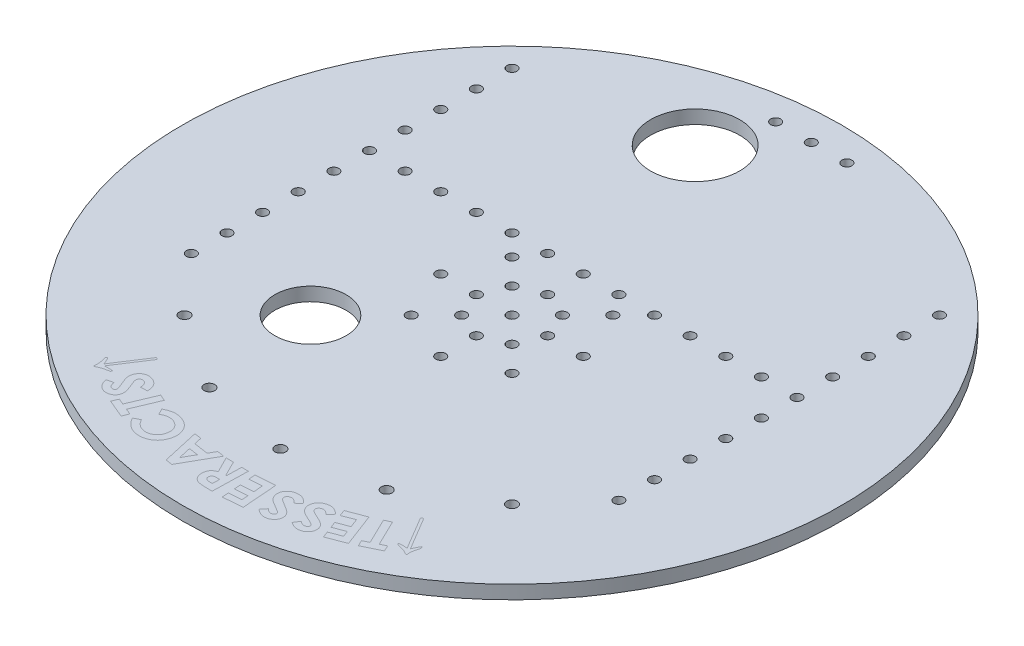
SolidWorks part; units mm, degrees
material "Balsa"
ref_plane "Front Plane" through (0, 0, 0) normal (0, 0, 1) x (1, 0, 0)
ref_plane "Top Plane" through (0, 0, 0) normal (0, 1, 0) x (1, 0, 0)
ref_plane "Right Plane" through (0, 0, 0) normal (1, 0, 0) x (0, 0, -1)
sketch "Sketch1" plane through (0, 0, 0) normal (0, 1, 0) x (1, 0, 0)
  circle A0 centre (0, 0) radius 117.475
  dimension "D1" = 234.95
extrude "Boss-Extrude1" add sketch "Sketch1" against normal blind 4.826
sketch "Sketch3" plane through (0, 0, 0) normal (0, 1, 0) x (1, 0, 0)
  line L1 (-114.4075, 26.67) -> (-88.9, 26.67)
  line L2 (0, -92.075) -> (0, -117.475)
  line L3 (-88.9, -26.67) -> (-88.9, 26.67)
  line L4 (0, 0) -> (-88.9, 0) construction
  line L5 (0, 0) -> (0, -117.475) construction
  line L6 (0, 0) -> (0, 117.475) construction
  line L8 (-88.9, -26.67) -> (-114.4075, -26.67)
  line L10 (-84.6624, -36.195) -> (-111.76, -36.195)
  arc A0 (-114.4075, 26.67) -> (-114.4075, -26.67) centre (0, 0) ccw
  circle A1 centre (0, 0) radius 117.475 construction
  arc A3 (-84.6624, -36.195) -> (0, -92.075) centre (0, 0) ccw
  arc A4 (-111.76, -36.195) -> (0, -117.475) centre (0, 0) ccw
  dimension "D1" = 88.9
  dimension "D2" = 53.34
  dimension "D4" = 9.525
  dimension "D5" = 25.4
extrude "Cut-Extrude4" [suppressed] cut sketch "Sketch3" against normal through all
fillet "Fillet1" [suppressed] radius 2.54
mirror "Mirror1" [suppressed] about plane through (0, 0, 0) normal (1, 0, 0)
sketch "Sketch4" plane through (0, 0, 0) normal (0, 1, 0) x (1, 0, 0)
  line L0 (-76.2, 38.1) -> (-76.2, 25.4) construction
  line L1 (-76.2, 25.4) -> (-76.2, 12.7) construction
  line L2 (-76.2, 12.7) -> (-76.2, 0) construction
  line L3 (-76.2, 0) -> (-76.2, -12.7) construction
  line L4 (-76.2, -12.7) -> (-76.2, -25.4) construction
  line L5 (-76.2, -25.4) -> (-76.2, -38.1) construction
  line L6 (0, 0) -> (-76.2, 0) construction
  line L12 (-76.2, 76.2) -> (-76.2, 63.5) construction
  line L13 (-76.2, 63.5) -> (-76.2, 50.8) construction
  line L14 (-76.2, 50.8) -> (-76.2, 38.1) construction
  circle A0 centre (-76.2, 0) radius 1.778
  circle A1 centre (-76.2, 12.7) radius 1.778
  circle A2 centre (-76.2, 25.4) radius 1.778
  circle A3 centre (-76.2, 38.1) radius 1.778
  circle A4 centre (-76.2, -12.7) radius 1.778
  circle A5 centre (-76.2, -25.4) radius 1.778
  circle A6 centre (-76.2, -38.1) radius 1.778
  circle A7 centre (-76.2, 50.8) radius 1.778
  circle A8 centre (-76.2, 63.5) radius 1.778
  circle A9 centre (-76.2, 76.2) radius 1.778
  dimension "D2" = 3.556
  dimension "D1" = 12.7
  dimension "D3" = 76.2
extrude "Cut-Extrude5" cut sketch "Sketch4" against normal through all
mirror "Mirror3" about plane through (0, 0, 0) normal (1, 0, 0) of "Cut-Extrude5"
sketch "Sketch5" plane through (0, 0, 0) normal (0, 1, 0) x (1, 0, 0)
  circle A0 centre (0, 0) radius 1.778
  dimension "D1" = 3.556
extrude "Cut-Extrude6" cut sketch "Sketch5" against normal through all
sketch "Sketch6" plane through (0, 0, 0) normal (0, 1, 0) x (1, 0, 0)
  line L0 (0, 0) -> (0, 25.4) construction
  line L1 (0, 25.4) -> (12.7, 25.4) construction
  line L2 (12.7, 25.4) -> (25.4, 25.4) construction
  line L3 (25.4, 25.4) -> (38.1, 25.4) construction
  line L4 (-38.1, 25.4) -> (-50.8, 25.4) construction
  line L5 (38.1, 25.4) -> (50.8, 25.4) construction
  line L6 (0, 25.4) -> (-12.7, 25.4) construction
  line L7 (-12.7, 25.4) -> (-25.4, 25.4) construction
  line L8 (-25.4, 25.4) -> (-38.1, 25.4) construction
  line L9 (-50.8, 25.4) -> (-63.5, 25.4) construction
  line L10 (50.8, 25.4) -> (63.5, 25.4) construction
  line L11 (0, 106.68) -> (12.7, 106.68) construction
  line L12 (12.7, 106.68) -> (25.4, 106.68) construction
  line L13 (25.4, 106.68) -> (38.1, 106.68) construction
  line L14 (-38.1, 106.68) -> (-50.8, 106.68) construction
  line L15 (38.1, 106.68) -> (50.8, 106.68) construction
  line L16 (0, 106.68) -> (-12.7, 106.68) construction
  line L17 (-12.7, 106.68) -> (-25.4, 106.68) construction
  line L18 (-25.4, 106.68) -> (-38.1, 106.68) construction
  line L19 (-50.8, 106.68) -> (-63.5, 106.68) construction
  line L20 (50.8, 106.68) -> (63.5, 106.68) construction
  line L21 (0, 25.4) -> (0, 106.68) construction
  circle A0 centre (0, 25.4) radius 1.778
  circle A1 centre (-12.7, 25.4) radius 1.778
  circle A2 centre (-25.4, 25.4) radius 1.778
  circle A3 centre (-38.1, 25.4) radius 1.778
  circle A4 centre (12.7, 25.4) radius 1.778
  circle A5 centre (25.4, 25.4) radius 1.778
  circle A6 centre (38.1, 25.4) radius 1.778
  circle A7 centre (-50.8, 25.4) radius 1.778
  circle A8 centre (50.8, 25.4) radius 1.778
  circle A9 centre (-63.5, 25.4) radius 1.778
  circle A10 centre (63.5, 25.4) radius 1.778
  circle A11 centre (0, 106.68) radius 1.778
  circle A12 centre (-12.7, 106.68) radius 1.778
  circle A13 centre (-25.4, 106.68) radius 1.778 construction
  circle A14 centre (-38.1, 106.68) radius 1.778 construction
  circle A15 centre (12.7, 106.68) radius 1.778
  circle A16 centre (25.4, 106.68) radius 1.778 construction
  circle A17 centre (38.1, 106.68) radius 1.778 construction
  circle A18 centre (-50.8, 106.68) radius 1.778 construction
  circle A19 centre (50.8, 106.68) radius 1.778 construction
  circle A20 centre (-63.5, 106.68) radius 1.778 construction
  circle A21 centre (63.5, 106.68) radius 1.778 construction
  dimension "D1" = 3.556
  dimension "D4" = 3.556
  dimension "D2" = 12.7
  dimension "D3" = 25.4
  dimension "D5" = 12.7
  dimension "D6" = 81.28
extrude "Cut-Extrude7" cut sketch "Sketch6" against normal through all
sketch "Sketch9" plane through (0, 0, 0) normal (0, 1, 0) x (1, 0, 0)
  line L4 (0, -82.55) -> (0, 0) construction
  circle A1 centre (0, -82.55) radius 1.905
  dimension "D2" = 3.81
  dimension "D1" = 82.55
extrude "Cut-Extrude10" cut sketch "Sketch9" against normal through all
pattern_circular "CirPattern1" count 3 over 45 about axis through (0, -4.826, 0) along (0, 1, 0) of "Cut-Extrude10"
pattern_circular "CirPattern2" count 3 over 45 about axis through (0, -4.826, 0) along (0, 1, 0) of "Cut-Extrude10" reverse direction yes
sketch "Sketch12" plane through (0, 0, 0) normal (0, 1, 0) x (1, 0, 0)
  text T0 "<b>MSE2202B       TRON UWO 2018</b>\r\n<b>TESSERACT COLLECTING ROBOT</b>\r\n<b>ver 2.0.0</b>\r\n<b>JdR CB TW MH</b>" font "Century Gothic" height 5.842
wrap "Wrap1" [suppressed] sketch "Sketch12" source sketch "Sketch12"
sketch "Sketch7" plane through (0, 0, 0) normal (0, 1, 0) x (1, 0, 0)
  line L0 (-8.9803, 8.9803) -> (0, 0) construction
  line L1 (0, 0) -> (8.9803, -8.9803) construction
  line L3 (8.9803, 8.9803) -> (0, 0) construction
  line L4 (0, 0) -> (-8.9803, -8.9803) construction
  line L6 (-12.7, 0) -> (0, 0) construction
  line L7 (0, 0) -> (0, 12.7) construction
  line L9 (12.7, 0) -> (0, 0) construction
  line L10 (0, 0) -> (0, -12.7) construction
  circle A0 centre (0, 12.7) radius 1.778
  circle A1 centre (12.7, 0) radius 1.778
  circle A2 centre (0, -12.7) radius 1.778
  circle A3 centre (-12.7, 0) radius 1.778
  circle A4 centre (-8.9803, 8.9803) radius 1.778
  circle A5 centre (8.9803, 8.9803) radius 1.778
  circle A6 centre (8.9803, -8.9803) radius 1.778
  circle A7 centre (-8.9803, -8.9803) radius 1.778
  dimension "D1" = 45
  dimension "D2" = 3.556
  dimension "D3" = 12.7
extrude "Cut-Extrude8" cut sketch "Sketch7" against normal through all
sketch "Sketch8" plane through (0, 0, 0) normal (0, 1, 0) x (1, 0, 0)
  line L0 (0, 0) -> (-35.921, -35.921) construction
  line L1 (-35.921, -35.921) -> (-35.921, -1.2798) construction
  circle A0 centre (-35.921, -35.921) radius 12.7
  dimension "D3" = 25.4
  dimension "D1" = 45
  dimension "D2" = 50.8
extrude "Cut-Extrude9" cut sketch "Sketch8" against normal through all
sketch "Sketch10" plane through (0, 0, 0) normal (0, 1, 0) x (1, 0, 0)
  line L0 (-19.812, 85.09) -> (-19.812, 0) construction
  line L1 (-19.812, 0) -> (0, 0) construction
  circle A0 centre (-19.812, 85.09) radius 15.875
  dimension "D1" = 31.75
  dimension "D2" = 85.09
  dimension "D3" = 19.812
extrude "Cut-Extrude11" cut sketch "Sketch10" against normal through all
sketch "Sketch14" plane through (0, 0, 0) normal (0, 1, 0) x (1, 0, 0)
  line L0 (0, 0) -> (-55.6246, -77.3206) construction
  line L1 (-55.6246, -77.3206) -> (55.6246, -77.3206) construction
  line L2 (55.6246, -77.3206) -> (0, 0) construction
  arc A0 (-55.6246, -77.3206) -> (55.6246, -77.3206) centre (0, 0) ccw construction
  text T0 "<b>↑TESSERACTS↑</b>" font "Century Gothic" height 12.7
  dimension "D1" = 95.25
wrap "Wrap2" sketch "Sketch14" wrap type scribe source sketch "Sketch14" face at (-19.812, 0, -69.215)
sketch "Sketch15" plane through (0, 0, 0) normal (0, 1, 0) x (1, 0, 0)
  line L0 (0, 0) -> (25.4, 0) construction
  circle A0 centre (25.4, 0) radius 1.778
  circle A1 centre (17.9605, -17.9605) radius 1.778
  circle A2 centre (0, -25.4) radius 1.778
  circle A3 centre (-17.9605, -17.9605) radius 1.778
  circle A4 centre (-25.4, 0) radius 1.778
  circle A5 centre (-17.9605, 17.9605) radius 1.778
  circle A6 centre (0, 25.4) radius 1.778
  circle A7 centre (17.9605, 17.9605) radius 1.778
  point P20 (0, 0)
  dimension "D2" = 3.556
  dimension "D1" = 25.4
  dimension "D3" = 8
extrude "Cut-Extrude12" cut sketch "Sketch15" against normal through all
